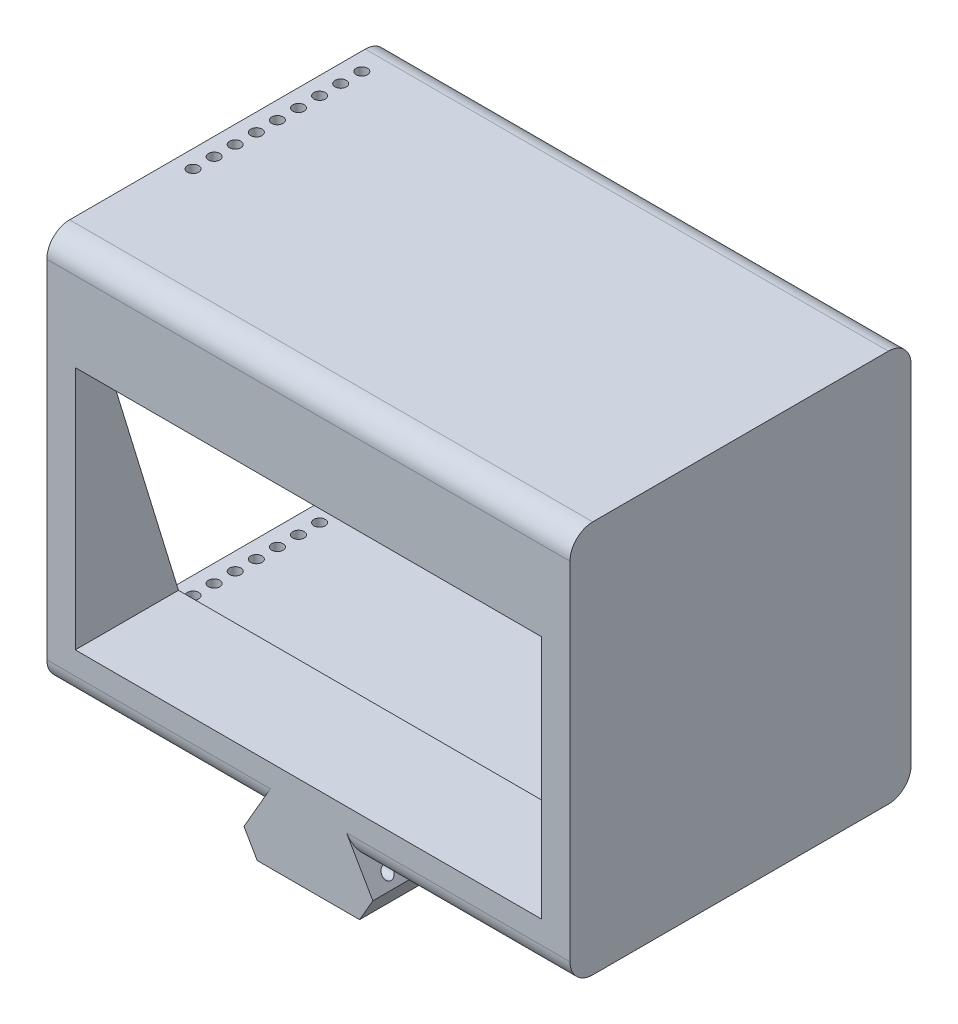
SolidWorks part; units mm, degrees
ref_plane "Front Plane" through (0, 0, 0) normal (0, 0, 1) x (1, 0, 0)
ref_plane "Top Plane" through (0, 0, 0) normal (0, 1, 0) x (1, 0, 0)
ref_plane "Right Plane" through (0, 0, 0) normal (1, 0, 0) x (0, 0, -1)
sketch "Sketch4" plane through (0, 0, 0) normal (1, 0, 0) x (0, 0, -1)
  line L1 (-30, 32.5) -> (30, 32.5)
  line L2 (-30, 32.5) -> (-30, -36.5)
  line L3 (-30, -36.5) -> (30, -36.5)
  line L4 (30, 32.5) -> (30, -36.5)
  dimension "D1" = 60
  dimension "D2" = 69
  dimension "D3" = 32.5
  dimension "D4" = 30
sketch "Sketch5" plane through (0, 0, 0) normal (1, 0, 0) x (0, 0, -1)
  line L0 (-25, 27.5) -> (-25, 14.5)
  line L1 (-25, 14.5) -> (-10.6307, -32.5)
  line L2 (-10.6307, -32.5) -> (25, -32.5)
  line L3 (25, -32.5) -> (25, 27.5)
  line L4 (25, 27.5) -> (-25, 27.5)
  line L5 (-30, 32.5) -> (-30, -36.5) construction
  line L6 (30, 32.5) -> (30, -36.5) construction
  line L7 (-30, 32.5) -> (30, 32.5) construction
  point P2 (0, 0)
  dimension "D1" = 107
  dimension "D2" = 13
  dimension "D3" = 60
  dimension "D4" = 50
  dimension "D5" = 25
  dimension "D6" = 27.5
  dimension "D7" = 5
  dimension "D8" = 5
  dimension "D9" = 5
extrude "Base" add sketch "Sketch4" along normal blind 46 and the other way blind 46
extrude "LIDAR" cut sketch "Sketch5" against normal up to surface (46 mm away) and the other way blind 41 up to face at (-46, -2, 0)
sketch "Sketch6" plane through (0, 0, 0) normal (0, 0, 1) x (1, 0, 0)
  line L0 (-46, 32.5) -> (-46, -36.5) construction
  line L1 (-41, 14.5) -> (41, 14.5)
  line L2 (-41, 14.5) -> (-41, -28.5)
  line L3 (-41, -28.5) -> (41, -28.5)
  line L4 (41, 14.5) -> (41, -28.5)
  line L5 (46, 32.5) -> (46, -36.5) construction
  line L6 (-46, 32.5) -> (46, 32.5) construction
  line L7 (-46, -36.5) -> (46, -36.5) construction
  dimension "D1" = 5
  dimension "D2" = 5
  dimension "D3" = 18
  dimension "D4" = 8
extrude "HoleFrontBack" cut sketch "Sketch6" against normal through all both and the other way through all
sketch "Sketch7" plane through (0, 0, 0) normal (0, 0, 1) x (1, 0, 0)
  line L0 (-9, -36.5) -> (9, -36.5)
  line L1 (-46, -36.5) -> (46, -36.5) construction
  line L2 (0, -33) -> (0, 33) construction
  line L3 (9, -36.5) -> (11.335, -40.5443)
  line L4 (11.335, -40.5443) -> (9, -44.5887)
  line L5 (9, -44.5887) -> (-9, -44.5887)
  line L6 (-9, -44.5887) -> (-11.335, -40.5443)
  line L7 (-11.335, -40.5443) -> (-9, -36.5)
  point P6 (0, 0)
  point P11 (0, 0)
  dimension "D1" = 18
  dimension "D2" = 9
  dimension "D3" = 120
  dimension "D4" = 120
  dimension "D5" = 120
  dimension "D6" = 120
  dimension "D7" = 18
  dimension "D8" = 4.67
extrude "Rail" add sketch "Sketch7" along normal up to surface (30 mm away) and the other way up to surface (30 mm away) up to face at (0, -7, 30) other way up to face at (0, -7, -30)
sketch "Sketch8" plane through (0, 0, 0) normal (1, 0, 0) x (0, 0, -1)
  line L0 (-30, -40.5443) -> (-30, -36.5) construction
  line L1 (-30, -36.5) -> (30, -36.5) construction
  circle A0 centre (-26.29, -38.6) radius 1
  dimension "D1" = 2
  dimension "D2" = 3.71
  dimension "D3" = 2.1
extrude "RailHole" cut sketch "Sketch8" against normal through all both and the other way through all
pattern_linear "LPattern1" count 15 spacing 3.71 along (0, 0, -1) of "RailHole"
fillet "Fillet2" radius 4 6 edges at (0, 32.5, -30) (-27.5, -36.5, -30) (27.5, -36.5, -30) (-27.5, -36.5, 30) (27.5, -36.5, 30) (0, 32.5, 30)
sketch "Sketch9" plane through (0, 0, 0) normal (0, 1, 0) x (1, 0, 0)
  line L0 (-46, 26) -> (-46, -26) construction
  line L1 (46, 26) -> (-46, 26) construction
  circle A0 centre (-42.9, 22.29) radius 1
  dimension "D1" = 2
  dimension "D2" = 3.1
  dimension "D3" = 3.71
extrude "Safety" cut sketch "Sketch9" along normal up to surface (32.5 mm away) and the other way blind 34.6 up to face at (0, 32.5, 0)
pattern_linear "LPattern2" count 9 spacing 3.71 along (0, 0, 1) of "Safety"
